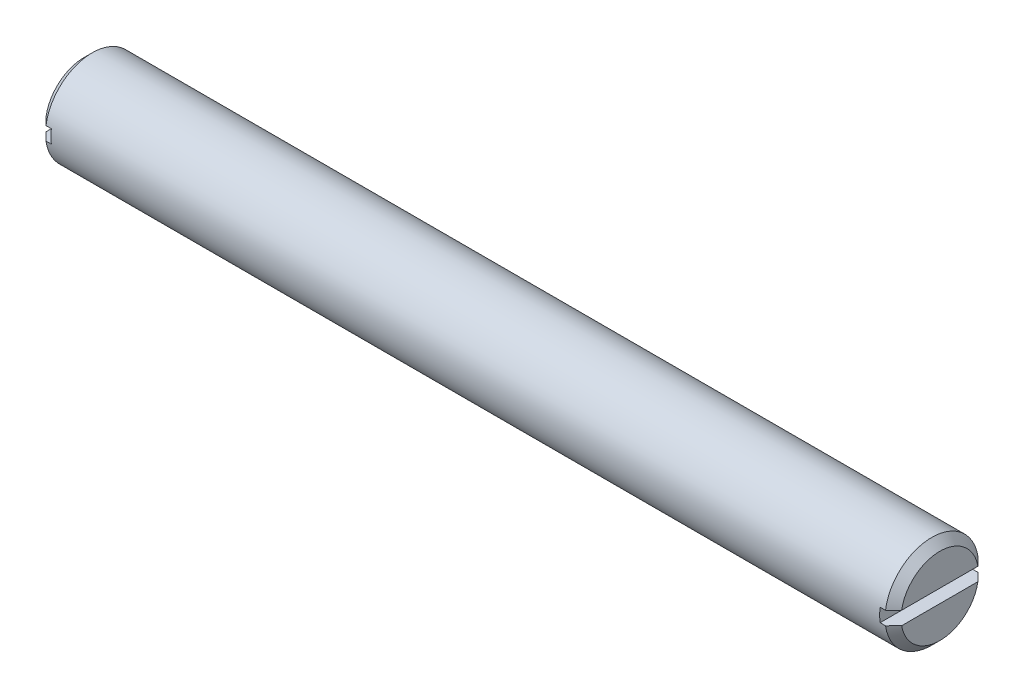
SolidWorks part; units mm, degrees
ref_plane "Front Plane" through (0, 0, 0) normal (0, 0, 1) x (1, 0, 0)
ref_plane "Top Plane" through (0, 0, 0) normal (0, 1, 0) x (1, 0, 0)
ref_plane "Right Plane" through (0, 0, 0) normal (1, 0, 0) x (0, 0, -1)
sketch "Sketch1" plane through (0, 0, 0) normal (0, 0, 1) x (1, 0, 0)
  line L0 (-50.8, 0) -> (50.8, 0) construction
  line L1 (50.8, 5.5499) -> (50.8, -5.5499) construction
  line L2 (-50.8, 5.5499) -> (-50.8, -5.5499) construction
  point P6 (46.355, -5.5499)
  dimension "Thread Diameter" = 11.0998
  dimension "Length" = 101.6
  dimension "D1" = 4.445
sketch "Sketch2" plane through (0, 0, 0) normal (1, 0, 0) x (0, 0, -1)
  circle A0 centre (0, 0) radius 5.5499
extrude "Boss-Extrude1" add sketch "Sketch2" against normal up to vertex (50.8 mm away) and the other way up to vertex (50.8 mm away) up to point (-50.8, 0, 0) other way up to point (50.8, 0, 0)
sketch "Sketch3" plane through (50.8, 0, 0) normal (1, 0, 0) x (0, 0, -1)
  circle A1 centre (0, 0) radius 5.5499
  circle A2 centre (0, 0) radius 5.5499
  dimension "D1" = 0
curve "Helix/Spiral1" pitch 1.27 height 102.87 turns 81 parameters "Pitch"=1.27
chamfer "Chamfer1" distance 0.9525 angle 45 2 edges at (-50.8, 0, -5.5499) (50.8, 0, -5.5499)
sketch "Sketch4" plane through (0, 0, 0) normal (0, 0, 1) x (1, 0, 0)
  line L0 (50.7206, 5.6874) -> (51.3556, 4.5875) construction
  line L1 (51.3556, 4.5875) -> (51.9906, 5.6874) construction
  line L2 (51.9906, 5.6874) -> (50.7206, 5.6874) construction
  line L3 (51.3556, 5.6874) -> (51.3556, 5.5499) construction
  line L4 (51.3556, 4.5875) -> (51.3556, 4.725) construction
  line L5 (51.2763, 4.725) -> (51.435, 4.725) construction
  line L6 (50.8, 5.5499) -> (51.9113, 5.5499) construction
  line L7 (51.2763, 4.725) -> (50.7603, 5.6186)
  line L8 (51.2763, 4.725) -> (51.435, 4.725)
  line L9 (50.7603, 5.6186) -> (51.9509, 5.6186)
  line L10 (51.9509, 5.6186) -> (51.435, 4.725)
  point P13 (51.3556, 5.6186)
  dimension "D2" = 0.1588
sweep "Cut-Sweep3" [suppressed] cut profiles "Sketch4" path "Helix/Spiral1"
sketch "Sketch5" plane through (0, 0, 0) normal (0, 0, 1) x (1, 0, 0)
  line L0 (0, 0) -> (0, 5.5499) construction
  line L1 (49.8475, 5.5499) -> (-49.8475, 5.5499) construction
  line L2 (0, 0) -> (50.8, 0) construction
  line L3 (50.8, -4.5974) -> (50.8, 4.5974) construction
  line L4 (-49.2125, 0.7937) -> (-49.2125, -0.7937)
  line L5 (50.8, 0.7937) -> (49.2125, 0.7937)
  line L6 (50.8, 0.7937) -> (50.8, -0.7937)
  line L7 (50.8, -0.7937) -> (49.2125, -0.7937)
  line L8 (49.2125, 0.7937) -> (49.2125, -0.7937)
  line L9 (-50.8, -0.7937) -> (-49.2125, -0.7937)
  line L10 (-50.8, 0.7937) -> (-50.8, -0.7937)
  line L11 (-50.8, 0.7937) -> (-49.2125, 0.7937)
  dimension "D1" = 1.5875
extrude "Cut-Extrude1" cut sketch "Sketch5" against normal through all both and the other way through all
equation "\"D3@Helix/Spiral1\" = \"Length@Sketch1\"+\"Pitch@Helix/Spiral1\""
equation "\"D1@Chamfer1\" = \"Pitch@Helix/Spiral1\"*.75"
equation "\"D1@Sketch4\" = \"Pitch@Helix/Spiral1\""
equation "\"D2@Sketch4\" = \"D1@Sketch4\"/8"
equation "\"D1@Sketch1\" = \"Pitch@Helix/Spiral1\"*3.50"
